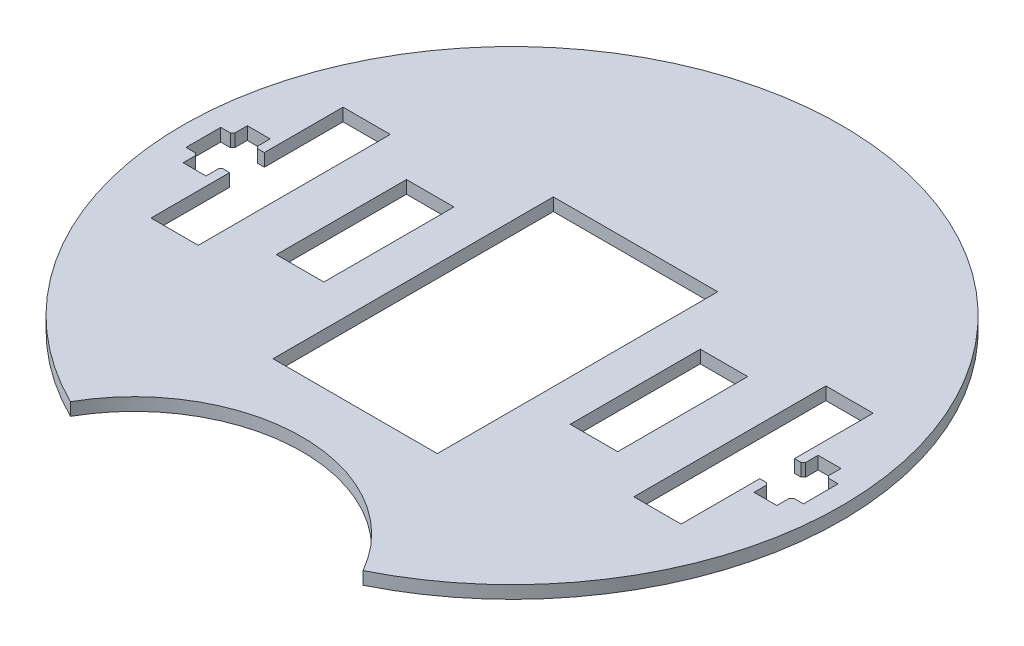
SolidWorks part; units mm, degrees
ref_plane "Front Plane" through (0, 0, 0) normal (0, 0, 1) x (1, 0, 0)
ref_plane "Top Plane" through (0, 0, 0) normal (0, 1, 0) x (1, 0, 0)
ref_plane "Right Plane" through (0, 0, 0) normal (1, 0, 0) x (0, 0, -1)
sketch "Sketch1" plane through (0, 0, 0) normal (0, 1, 0) x (1, 0, 0)
  line L0 (0, -86.0416) -> (-33.2911, -67.2064) construction
  line L1 (0, -86.0416) -> (0, 0) construction
  arc A0 (33.2911, -67.2064) -> (-33.2911, -67.2064) centre (0, 0) ccw
  arc A1 (33.2911, -67.2064) -> (-33.2911, -67.2064) centre (0, -86.0416) ccw
  dimension "D1" = 150
  dimension "D2" = 76.5
  dimension "D3" = 60.5
extrude "Boss-Extrude1" add sketch "Sketch1" along normal blind 2.9
sketch "solenoid placement" plane through (0, 2.9, 0) normal (0, 1, 0) x (1, 0, 0)
  line L0 (0, 0) -> (0, -36) construction
  line L1 (0, -36) -> (0, -47.7916) construction
  line L2 (-19, -36) -> (19, -36) construction
  line L3 (-19, -36) -> (-19, 28.4) construction
  line L4 (-19, 28.4) -> (19, 28.4) construction
  line L5 (19, -36) -> (19, 28.4) construction
  line L6 (-18.7, 28.1) -> (18.7, 28.1)
  line L7 (18.7, -35.7) -> (18.7, 28.1)
  line L8 (-18.7, -35.7) -> (18.7, -35.7)
  line L9 (-18.7, -35.7) -> (-18.7, 28.1)
  circle A1 centre (0, 0) radius 75 construction
  arc A2 (33.2911, -67.2064) -> (-33.2911, -67.2064) centre (0, 0) ccw construction
  arc A3 (33.2911, -67.2064) -> (-33.2911, -67.2064) centre (0, -86.0416) ccw construction
  dimension "D1" = 64.4
  dimension "D2" = 36
  dimension "D3" = 0.3
  dimension "D4" = 38
extrude "Cut-Extrude1" cut sketch "solenoid placement" against normal through all
sketch "Sketch2" plane through (0, 2.9, 0) normal (0, 1, 0) x (1, 0, 0)
  line L0 (49.8627, -21.5538) -> (49.8627, 21.5538) construction
  line L1 (-60.0227, -21.5538) -> (-49.8627, -21.5538) construction
  line L2 (-60.0227, -21.5538) -> (-60.0227, 21.5538) construction
  line L3 (-60.0227, 21.5538) -> (-49.8627, 21.5538) construction
  line L4 (-49.8627, -21.5538) -> (-49.8627, 21.5538) construction
  line L5 (60.0227, 21.5538) -> (49.8627, 21.5538) construction
  line L6 (60.0227, -21.5538) -> (60.0227, 21.5538) construction
  line L7 (60.0227, -21.5538) -> (49.8627, -21.5538) construction
  line L8 (60.3227, -21.8538) -> (60.3227, 21.8538)
  line L9 (60.3227, -21.8538) -> (49.5627, -21.8538)
  line L10 (49.5627, -21.8538) -> (49.5627, 21.8538)
  line L11 (60.3227, 21.8538) -> (49.5627, 21.8538)
  line L12 (0, 0) -> (0, 75) construction
  line L13 (-60.3227, 21.8538) -> (-49.5627, 21.8538)
  line L14 (-49.5627, -21.8538) -> (-49.5627, 21.8538)
  line L15 (-60.3227, -21.8538) -> (-49.5627, -21.8538)
  line L16 (-60.3227, -21.8538) -> (-60.3227, 21.8538)
  arc A0 (33.2911, -67.2064) -> (-33.2911, -67.2064) centre (0, 0) ccw construction
extrude "Cut-Extrude2" cut sketch "Sketch2" against normal through all
sketch "Sketch3" plane through (0, 2.9, 0) normal (0, 1, 0) x (1, 0, 0)
  line L0 (-38.8327, -14.8) -> (-28.0327, -14.8)
  line L1 (-39.0327, -15) -> (-27.8327, -15) construction
  line L2 (-39.0327, -15) -> (-39.0327, 15) construction
  line L3 (-39.0327, 15) -> (-27.8327, 15) construction
  line L4 (-27.8327, -15) -> (-27.8327, 15) construction
  line L5 (-28.0327, -14.8) -> (-28.0327, 14.8)
  line L6 (-38.8327, 14.8) -> (-28.0327, 14.8)
  line L7 (-38.8327, -14.8) -> (-38.8327, 14.8)
  line L8 (0, 0) -> (0, 75) construction
  line L9 (27.8327, -15) -> (27.8327, 15) construction
  line L10 (39.0327, 15) -> (27.8327, 15) construction
  line L11 (39.0327, -15) -> (39.0327, 15) construction
  line L12 (39.0327, -15) -> (27.8327, -15) construction
  line L13 (38.8327, -14.8) -> (38.8327, 14.8)
  line L14 (38.8327, 14.8) -> (28.0327, 14.8)
  line L15 (28.0327, -14.8) -> (28.0327, 14.8)
  line L16 (38.8327, -14.8) -> (28.0327, -14.8)
  arc A0 (33.2911, -67.2064) -> (-33.2911, -67.2064) centre (0, 0) ccw construction
  point P16 (0, 0)
  point P17 (0, 0)
  point P26 (0, 0)
  point P27 (0, 0)
  point P28 (0, 0)
  point P29 (0, 0)
  point P30 (0, 0)
  point P31 (0, 0)
  point P32 (-40.1435, -14.5813)
  point P34 (0, 0)
  point P35 (-28.0046, 15.6931)
extrude "Cut-Extrude3" cut sketch "Sketch3" against normal through all
sketch "Sketch5" plane through (0, 2.9, 0) normal (0, 1, 0) x (1, 0, 0)
  line L0 (-62.1527, 4.15) -> (-67.7527, 4.15) construction
  line L1 (-67.7527, 7.5) -> (-62.1527, 7.5) construction
  line L2 (-67.7527, 7.5) -> (-67.7527, 4.15) construction
  line L3 (-67.7527, -7.5) -> (-62.1527, -7.5) construction
  line L4 (-62.1527, 7.5) -> (-62.1527, 4.15) construction
  line L5 (-62.1527, -4.15) -> (-67.7527, -4.15) construction
  line L6 (-62.1527, 4.15) -> (-67.7527, 4.15) construction
  line L7 (-62.1527, -4.15) -> (-67.7527, -4.15) construction
  line L8 (-67.7527, 4.15) -> (-70.4527, 4.15) construction
  line L9 (-70.4527, 4.15) -> (-70.4527, -4.15) construction
  line L10 (-70.4527, -4.15) -> (-67.7527, -4.15) construction
  line L11 (-62.1527, -4.15) -> (-59.4527, -4.15) construction
  line L12 (-59.4527, -4.15) -> (-59.4527, 4.15) construction
  line L13 (-59.4527, 4.15) -> (-62.1527, 4.15) construction
  line L14 (-67.7527, -4.15) -> (-67.7527, -7.5) construction
  line L15 (-62.1527, -4.15) -> (-62.1527, -7.5) construction
  line L16 (-67.5527, 7.3) -> (-62.3527, 7.3)
  line L17 (-62.3527, 7.3) -> (-62.3527, 3.95)
  line L18 (-59.6527, 3.95) -> (-62.3527, 3.95)
  line L19 (-59.6527, -3.95) -> (-59.6527, 3.95)
  line L20 (-62.3527, -3.95) -> (-59.6527, -3.95)
  line L21 (-62.3527, -3.95) -> (-62.3527, -7.3)
  line L22 (-67.5527, -7.3) -> (-62.3527, -7.3)
  line L23 (-67.5527, -3.95) -> (-67.5527, -7.3)
  line L24 (-70.2527, -3.95) -> (-67.5527, -3.95)
  line L25 (-70.2527, 3.95) -> (-70.2527, -3.95)
  line L26 (-67.5527, 3.95) -> (-70.2527, 3.95)
  line L27 (-67.5527, 7.3) -> (-67.5527, 3.95)
  line L28 (0, 0) -> (0, 75) construction
  line L29 (62.1527, -4.15) -> (62.1527, -7.5) construction
  line L30 (67.7527, -4.15) -> (67.7527, -7.5) construction
  line L31 (59.4527, 4.15) -> (62.1527, 4.15) construction
  line L32 (59.4527, -4.15) -> (59.4527, 4.15) construction
  line L33 (62.1527, -4.15) -> (59.4527, -4.15) construction
  line L34 (70.4527, -4.15) -> (67.7527, -4.15) construction
  line L35 (70.4527, 4.15) -> (70.4527, -4.15) construction
  line L36 (67.7527, 4.15) -> (70.4527, 4.15) construction
  line L37 (62.1527, -4.15) -> (67.7527, -4.15) construction
  line L38 (62.1527, 4.15) -> (67.7527, 4.15) construction
  line L39 (62.1527, 7.5) -> (62.1527, 4.15) construction
  line L40 (67.7527, -7.5) -> (62.1527, -7.5) construction
  line L41 (67.7527, 7.5) -> (67.7527, 4.15) construction
  line L42 (67.7527, 7.5) -> (62.1527, 7.5) construction
  line L43 (67.5527, 7.3) -> (67.5527, 3.95)
  line L44 (67.5527, 3.95) -> (70.2527, 3.95)
  line L45 (70.2527, 3.95) -> (70.2527, -3.95)
  line L46 (70.2527, -3.95) -> (67.5527, -3.95)
  line L47 (67.5527, -3.95) -> (67.5527, -7.3)
  line L48 (67.5527, -7.3) -> (62.3527, -7.3)
  line L49 (62.3527, -3.95) -> (62.3527, -7.3)
  line L50 (62.3527, -3.95) -> (59.6527, -3.95)
  line L51 (59.6527, -3.95) -> (59.6527, 3.95)
  line L52 (59.6527, 3.95) -> (62.3527, 3.95)
  line L53 (62.3527, 7.3) -> (62.3527, 3.95)
  line L54 (67.5527, 7.3) -> (62.3527, 7.3)
  arc A0 (33.2911, -67.2064) -> (-33.2911, -67.2064) centre (0, 0) ccw construction
  point P15 (-59.4527, 0)
  point P17 (59.4527, 0)
  dimension "D1" = 11
extrude "Cut-Extrude4" cut sketch "Sketch5" against normal through all
chamfer "Chamfer1" distance 0.5 angle 45 8 edges at (67.5527, 1.45, 3.95) (67.5527, 1.45, -3.95) (62.3527, 1.45, 3.95) (62.3527, 1.45, -3.95) (-62.3527, 1.45, 3.95) (-67.5527, 1.45, 3.95) (-62.3527, 1.45, -3.95) (-67.5527, 1.45, -3.95)
equation "\"smallPulleyTeeth\"= 15"
equation "\"largePulleyTeeth\"= 30"
equation "\"eighthThick\"= 2.9mm"
equation "\"sixteenthThick\" = 1.7mm"
equation "\"wheelEighthThick\"=3.0mm"
equation "\"quarterThick\"=5.6mm"
equation "\"OD\" = 150mm"
equation "\"puckAngle\" = 60.5deg"
equation "\"D1@Sketch1\"=\"OD\""
equation "\"puckDiam\" = 76.5mm"
equation "\"D2@Sketch1\"=\"puckDiam\""
equation "\"D3@Sketch1\"=\"puckAngle\""
equation "\"D1@Boss-Extrude1\"=\"eighthThick\""
equation "\"axlePress\" = 5.8mm"
equation "\"press\" = 0.2mm"
equation "\"D1@Sketch3\"=\"press\""
equation "\"wheelClear\" = 0.3mm"
equation "\"D1@Sketch2\"=\"wheelClear\""
equation "\"D2@Sketch5\"=\"press\""
